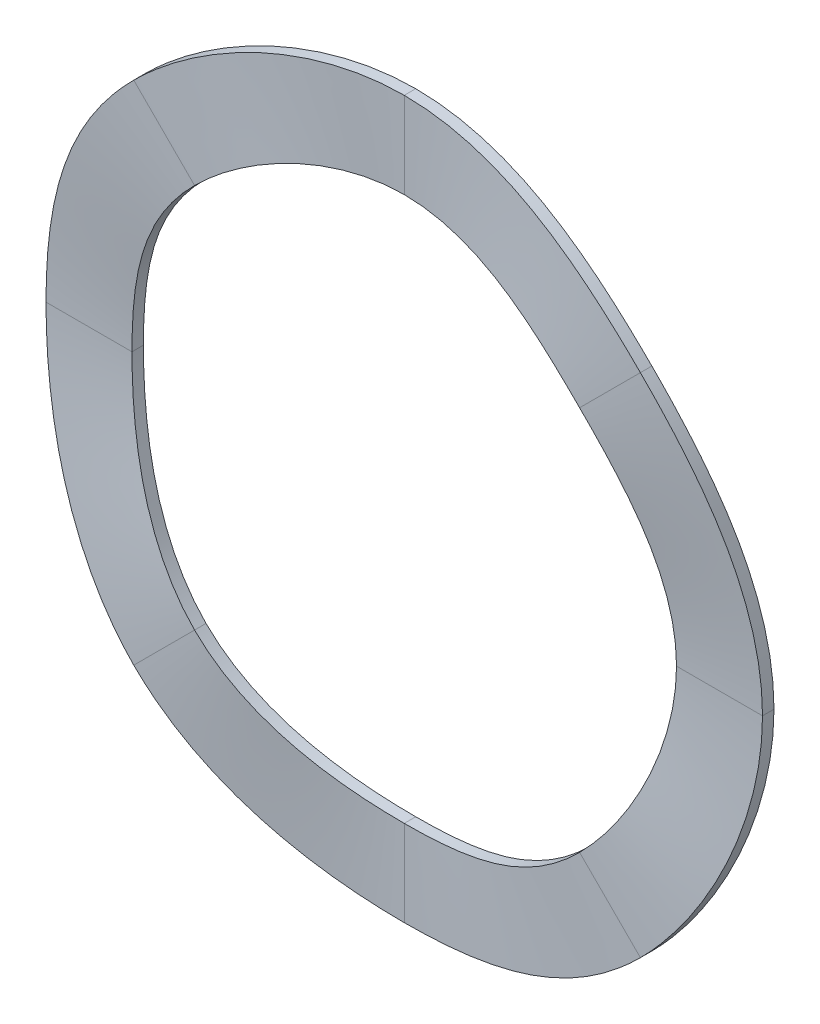
SolidWorks part; units mm, degrees
material "Acier allié inoxydable"
ref_plane "Plan de face" through (0, 0, 0) normal (0, 0, 1) x (1, 0, 0)
ref_plane "Plan de dessus" through (0, 0, 0) normal (0, 1, 0) x (1, 0, 0)
ref_plane "Plan de droite" through (0, 0, 0) normal (1, 0, 0) x (0, 0, -1)
ref_axis "Axe1" through (0, 0, 0) along (0, 0, 1)
sketch "Esquisse1" plane through (0, 0, 0) normal (0, 0, 1) x (1, 0, 0)
  line L0 (-12.5, 0) -> (-9.5, 0) construction
  line L1 (0, 0) -> (-7.7782, -7.7782) construction
  line L2 (0, 0) -> (-4.2095, -10.1627) construction
  circle A0 centre (0, 0) radius 12.5
  circle A1 centre (0, 0) radius 9.5
  circle A2 centre (0, 0) radius 11 construction
  point P5 (-11, 0)
  dimension "D1" = 25
  dimension "D2" = 19
  dimension "D3" = 45
  dimension "D4" = 22.5
ref_plane "Plan1" through (0, 0, 0) normal (-0.7071, 0.7071, 0) x (-0.7071, -0.7071, 0)
ref_plane "Plan2" through (0, 0, 0) normal (-0.9239, 0.3827, 0) x (-0.3827, -0.9239, 0)
sketch "Esquisse2" plane through (0, 0, 0) normal (-0.7071, 0.7071, 0) x (0.7071, 0.7071, 0)
  line L1 (-12.5, 0.5) -> (12.5, 0.5)
  line L2 (-12.5, 0.5) -> (-12.5, -0.5)
  line L3 (-12.5, -0.5) -> (12.5, -0.5)
  line L4 (12.5, 0.5) -> (12.5, -0.5)
  line L5 (-9.5, -0.1) -> (-9.5, 0) construction
  line L8 (-12.5, -0.1) -> (-9.5, -0.1) construction
  line L9 (-9.5, -0.1) -> (-9.5, -0.5) construction
  line L11 (0, 0.5) -> (0, 0.1) construction
  line L12 (-12.5, -0.1) -> (-9.5, -0.5) construction
  point P4 (-12.5, 0)
  point P5 (12.5, 0)
  dimension "D1" = 1
  dimension "D2" = 0.4
  dimension "D3" = 0.4
sketch "Esquisse3" plane through (0, 0, 0) normal (1, 0, 0) x (0, 0, -1)
  line L0 (0.1, -9.5) -> (0, -9.5) construction
  line L1 (0.5, -12.5) -> (0.1, -12.5)
  line L2 (0.5, -12.5) -> (0.5, -9.5)
  line L3 (0.5, -9.5) -> (0.1, -9.5)
  line L4 (0.1, -12.5) -> (0.1, -9.5)
  line L5 (0.1, -12.5) -> (0, -12.5) construction
  line L10 (0.1, -9.5) -> (0.5, -12.5) construction
sketch "Esquisse4" plane through (0, 0, 0) normal (-0.7071, 0.7071, 0) x (-0.7071, -0.7071, 0)
  line L1 (9.5, 0.1) -> (12.5, 0.1)
  line L2 (9.5, 0.1) -> (9.5, 0.5)
  line L3 (9.5, 0.5) -> (12.5, 0.5)
  line L4 (12.5, 0.1) -> (12.5, 0.5)
sketch "Esquisse5" plane through (0, 0, 0) normal (-0.9239, 0.3827, 0) x (-0.3827, -0.9239, 0)
  line L0 (9.5, 0.2) -> (12.5, -0.2) construction
  line L1 (12.5, 0.2) -> (9.5, 0.2)
  line L2 (12.5, 0.2) -> (12.5, -0.2)
  line L3 (12.5, -0.2) -> (9.5, -0.2)
  line L4 (9.5, 0.2) -> (9.5, -0.2)
  line L5 (0, -0.5) -> (0, -0.1) construction
  point P8 (12.5, 0)
loft "Lissage2" add profiles "Esquisse3", "Esquisse5", "Esquisse4" start constraint normal to profile start tangent length 1 end constraint normal to profile end tangent length 1 connector at (0, -12.5, -0.1) connector at (-4.7835, -11.5485, 0.2) connector at (-8.8388, -8.8388, 0.5)
mirror "Symétrie5" about plane through (0, 0, 0) normal (-0.7071, 0.7071, 0) of bodies 107
mirror "Symétrie6" about plane through (0, 0, 0) normal (0, 1, 0) of bodies 108
mirror "Symétrie7" about plane through (0, 0, 0) normal (1, 0, 0) of bodies 109
